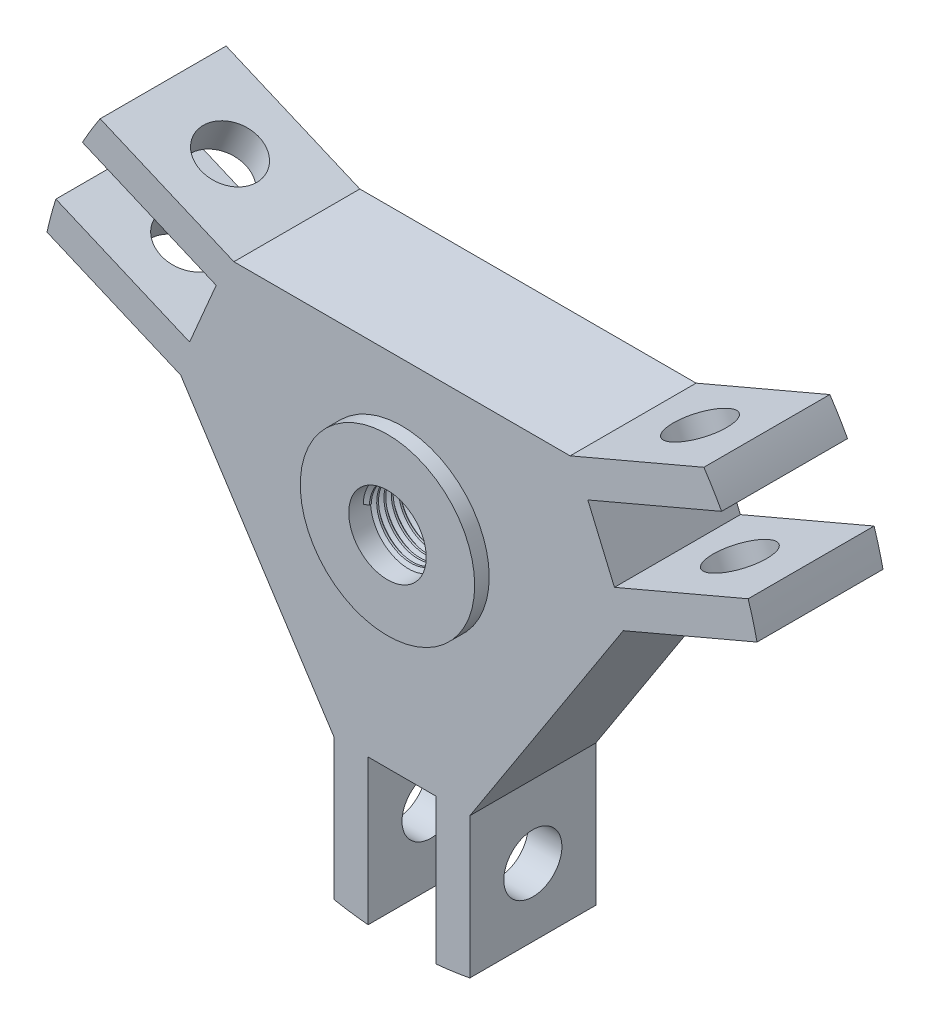
SolidWorks part; units mm, degrees
ref_plane "Front Plane" through (0, 0, 0) normal (0, 0, 1) x (1, 0, 0)
ref_plane "Top Plane" through (0, 0, 0) normal (0, 1, 0) x (1, 0, 0)
ref_plane "Right Plane" through (0, 0, 0) normal (1, 0, 0) x (0, 0, -1)
sketch "Sketch1" plane through (0, 0, 0) normal (0, 0, 1) x (1, 0, 0)
  line L0 (-34.7001, 30) -> (34.7001, 30)
  line L1 (96.1952, 40.98) -> (-16.5282, -7.0412) construction
  line L2 (14, -5.9641) -> (-69.2368, 29.4955) construction
  line L3 (-34.7001, 30) -> (-62.3, 41.7578)
  line L4 (14, -73.6817) -> (14, -44.6726)
  line L5 (-65.9551, 35.7062) -> (-38.3552, 23.9484)
  line L6 (-38.3552, 23.9484) -> (-43.8421, 11.0684)
  line L7 (-43.8421, 11.0684) -> (-71.442, 22.8262)
  line L8 (7, -74.6726) -> (7, -44.6726)
  line L9 (-73.2739, 15.9979) -> (-45.674, 4.2401)
  line L10 (73.2739, 15.9979) -> (45.674, 4.2401)
  line L11 (7, -44.6726) -> (-7, -44.6726)
  line L12 (43.8421, 11.0684) -> (71.442, 22.8262)
  line L13 (38.3552, 23.9484) -> (43.8421, 11.0684)
  line L14 (65.9551, 35.7062) -> (38.3552, 23.9484)
  line L15 (-7, -44.6726) -> (-7, -74.6726)
  line L16 (34.7001, 30) -> (62.3, 41.7578)
  line L17 (-14, -73.6817) -> (-14, -44.6726)
  line L18 (-61.3096, 10.901) -> (-48.5, 35.8789) construction
  line L19 (14, -59.6726) -> (-13.9977, -59.6726) construction
  line L20 (-14, -44.6726) -> (-45.674, 4.2401)
  line L21 (45.674, 4.2401) -> (14, -44.6726)
  circle A0 centre (0, 0) radius 18
  circle A1 centre (0, 0) radius 8
  arc A2 (-71.442, 22.8262) -> (-73.2739, 15.9979) centre (0, 0) ccw
  arc A3 (-62.3, 41.7578) -> (-65.9551, 35.7062) centre (0, 0) ccw
  arc A4 (65.9551, 35.7062) -> (62.3, 41.7578) centre (0, 0) ccw
  arc A5 (-14, -73.6817) -> (-7, -74.6726) centre (0, 0) ccw
  arc A6 (73.2739, 15.9979) -> (71.442, 22.8262) centre (0, 0) ccw
  arc A7 (7, -74.6726) -> (14, -73.6817) centre (0, 0) ccw
  point P8 (41.0986, 17.5084)
  point P27 (-41.0986, 17.5084)
  point P28 (-72.8211, 30.3861)
  dimension "D1" = 36
  dimension "D2" = 16
  dimension "D4" = 150
  dimension "D3" = 30
  dimension "D5" = 7
  dimension "D6" = 14
  dimension "D7" = 30
  dimension "D8" = 15
  dimension "D9" = 28
  dimension "D10" = 14
  dimension "D11" = 14
  dimension "D12" = 28
  dimension "D13" = 30
  dimension "D14" = 7
  dimension "D15" = 15
extrude "Boss-Extrude1" add sketch "Sketch1" along normal mid plane 26 contours L8 A7 L4 L21 L10 A6 L12 L13 L14 A4 L16 L0 L3 A3 L5 L6 L7 A2 L9 L20 L17 A5 L15 L11 A0 region at (0, 28.1283, 0)
extrude "Boss-Extrude2" add sketch "Sketch1<4>" along normal mid plane 32 contours A0 A1 region at (-17.4909, 0, 0)
sketch "Sketch1<4>" plane through (0, 0, 0) normal (0, 0, 1) x (1, 0, 0) same geometry as "Sketch1"
sketch "Sketch2" plane through (5.487, -12.8799, 0) normal (0.3919, -0.92, 0) x (0.92, 0.3919, 0)
  line L0 (73.6817, 13) -> (43.6817, 13) construction
  line L1 (43.6817, 13) -> (43.6817, -13) construction
  circle A0 centre (58.6817, 0) radius 6
  dimension "D1" = 13
  dimension "D2" = 15
  dimension "D3" = 12
extrude "Cut-Extrude1" cut sketch "Sketch2" against normal through all both and the other way through all
sketch "Sketch3" plane through (-5.487, -12.8799, 0) normal (-0.3919, -0.92, 0) x (0.92, -0.3919, 0)
  line L0 (-73.6817, 13) -> (-73.6817, -13) construction
  line L1 (-73.6817, 13) -> (-43.6817, 13) construction
  circle A0 centre (-58.6817, 0) radius 6
  dimension "D1" = 15
  dimension "D2" = 13
  dimension "D3" = 12
extrude "Cut-Extrude2" cut sketch "Sketch3" against normal through all both
sketch "Sketch4" plane through (-14, 0, 0) normal (-1, 0, 0) x (0, 0, 1)
  line L0 (-13, -73.6817) -> (-13, -44.6726) construction
  line L1 (13, -44.6726) -> (-13, -44.6726) construction
  circle A0 centre (0, -59.6726) radius 6
  dimension "D1" = 13
  dimension "D2" = 15
extrude "Cut-Extrude3" cut sketch "Sketch4" against normal through all both
thread "Thread1" pitch 1.5 method extrude profile "Thread Profile2" start angle 0, offset 3, length 26, pitch 1.5, diameter 16
ref_plane "Plane2" through (-8, 0, 13) normal (0, -1, 0) x (-1, 0, 0)
sketch "Thread Profile2" plane through (-8, 0, 13) normal (0, -1, 0) x (-1, 0, 0)
  line L0 (0, 0) -> (0, 1.5) construction
  line L11 (0, 0) -> (0, 1.3125)
  line L12 (0, 1.3125) -> (-0.8119, 0.8437)
  line L13 (-0.8119, 0.8437) -> (-0.8119, 0.4687)
  line L15 (-0.8119, 0.4687) -> (0, 0)
  line L17 (-0.8119, 0.6562) -> (0, 0.6562) construction
  point P2 (0, 0)
  dimension "Pitch" = 1.5
  dimension "Profile_Angle" = 60
  dimension "Profile_Land" = 0.375
  dimension "Profile_Height" = 0.8119
